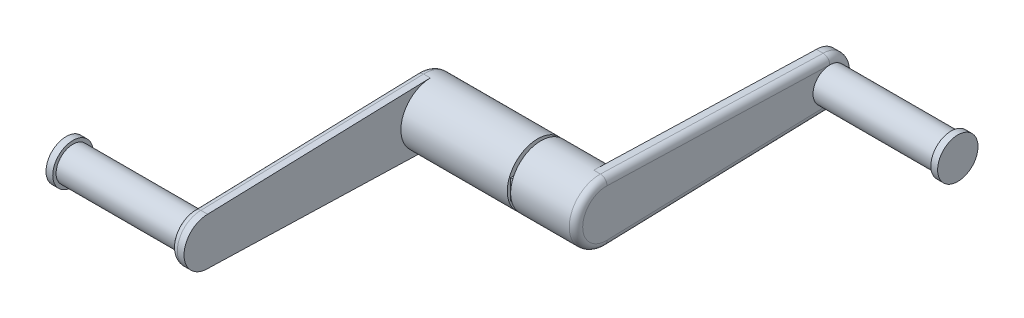
SolidWorks part; units mm, degrees
ref_plane "Front Plane" through (0, 0, 0) normal (0, 0, 1) x (1, 0, 0)
ref_plane "Top Plane" through (0, 0, 0) normal (0, 1, 0) x (1, 0, 0)
ref_plane "Right Plane" through (0, 0, 0) normal (1, 0, 0) x (0, 0, -1)
sketch "Sketch1" plane through (0, 0, 0) normal (1, 0, 0) x (0, 0, -1)
  circle A0 centre (0, 0) radius 338.5
  dimension "D1" = 677
sketch "Sketch2" plane through (0, 0, 0) normal (1, 0, 0) x (0, 0, -1)
  line L0 (-935.3702, 226.3146) -> (-163.5974, 226.3146) construction
  line L1 (-626.7849, -26.0893) -> (-626.7849, -67.6929) construction
  line L2 (-646.7849, -35.9173) -> (-633.3993, -35.9173)
  line L3 (-646.7849, -35.9173) -> (-646.7849, -50.9173)
  line L4 (-646.7849, -50.9173) -> (-633.3993, -50.9173)
  line L5 (-606.7849, -35.9173) -> (-606.7849, -50.9173)
  line L6 (-610.8111, -43.4173) -> (-642.1815, -43.4173) construction
  line L7 (-620.1705, -35.9173) -> (-606.7849, -35.9173)
  line L8 (-620.1705, -50.9173) -> (-606.7849, -50.9173)
  arc A0 (-633.3993, -50.9173) -> (-620.1705, -50.9173) centre (-626.7849, -43.4173) ccw
  arc A1 (-620.1705, -35.9173) -> (-633.3993, -35.9173) centre (-626.7849, -43.4173) ccw
  dimension "D1" = 20
  dimension "D2" = 15
  dimension "D3" = 40
  dimension "D4" = 7.5
  dimension "D5" = 20
sketch "Sketch3" plane through (0, 0, 0) normal (1, 0, 0) x (0, 0, -1)
  circle A0 centre (-626.7849, -43.4173) radius 22.5
  dimension "D1" = 45
extrude "Boss-Extrude1" add sketch "Sketch3" along normal blind 60 and the other way blind 60
sketch "Sketch4" plane through (60, 0, 0) normal (1, 0, 0) x (0, 0, -1)
  line L0 (-460.7849, -25.9173) -> (-626.1061, -20.9275)
  line L1 (-460.7849, -60.9173) -> (-626.1061, -65.907)
  arc A0 (-626.1061, -20.9275) -> (-626.1061, -65.907) centre (-626.7849, -43.4173) ccw
  arc A1 (-460.7849, -60.9173) -> (-460.7849, -25.9173) centre (-460.7849, -43.4173) ccw
  dimension "D1" = 45
  dimension "D2" = 35
  dimension "D3" = 166
extrude "Boss-Extrude2" add sketch "Sketch4" along normal blind 10
sketch "Sketch5" plane through (70, 0, 0) normal (1, 0, 0) x (0, 0, -1)
  circle A0 centre (-460.7849, -43.4173) radius 12.5
  dimension "D1" = 25
extrude "Boss-Extrude3" add sketch "Sketch5" along normal blind 90
sketch "Sketch6" plane through (160, 0, 0) normal (1, 0, 0) x (0, 0, -1)
  circle A0 centre (-460.7849, -43.4173) radius 15
  dimension "D1" = 30
extrude "Boss-Extrude4" add sketch "Sketch6" along normal blind 5
fillet "Fillet1" radius 5 4 edges at (70, -63.4121, 543.4455) (70, -43.4173, 649.2849) (70, -23.4224, 543.4455) (70, -43.4173, 443.2849)
sketch "Sketch7" plane through (-60, 0, 0) normal (-1, 0, 0) x (0, 0, 1)
  line L1 (792.7849, -25.9173) -> (627.4637, -20.9275)
  line L2 (792.7849, -60.9173) -> (627.4637, -65.907)
  arc A0 (627.4637, -20.9275) -> (627.4637, -65.907) centre (626.7849, -43.4173) ccw
  arc A1 (792.7849, -60.9173) -> (792.7849, -25.9173) centre (792.7849, -43.4173) ccw
  dimension "D1" = 45
  dimension "D3" = 35
  dimension "D2" = 166
extrude "Boss-Extrude5" add sketch "Sketch7" along normal blind 10
sketch "Sketch8" plane through (-70, 0, 0) normal (-1, 0, 0) x (0, 0, 1)
  circle A0 centre (792.7849, -43.4173) radius 12.5
  dimension "D1" = 25
extrude "Boss-Extrude6" add sketch "Sketch8" along normal blind 90
sketch "Sketch10" plane through (-160, 0, 0) normal (-1, 0, 0) x (0, 0, 1)
  circle A0 centre (792.7849, -43.4173) radius 15
  dimension "D1" = 30
extrude "Boss-Extrude7" add sketch "Sketch10" along normal blind 5
fillet "Fillet2" radius 5 4 edges at (-70, -63.4122, 710.1243) (-70, -43.4173, 604.2849) (-70, -43.4173, 810.2849) (-70, -23.4224, 710.1243)
ref_plane "Plane2" through (19, 0, 0) normal (1, 0, 0) x (0, 0, -1)
sketch "Sketch12" plane through (19, 0, 0) normal (1, 0, 0) x (0, 0, -1)
  line L0 (-620.1705, -35.9173) -> (-606.7849, -35.9173)
  line L1 (-646.7849, -35.9173) -> (-633.3993, -35.9173)
  line L2 (-646.7849, -35.9173) -> (-646.7849, -50.9173)
  line L3 (-646.7849, -50.9173) -> (-633.3993, -50.9173)
  line L4 (-606.7849, -35.9173) -> (-606.7849, -50.9173)
  line L5 (-620.1705, -50.9173) -> (-606.7849, -50.9173)
  arc A0 (-633.3993, -50.9173) -> (-620.1705, -50.9173) centre (-626.7849, -43.4173) ccw
  arc A1 (-620.1705, -35.9173) -> (-633.3993, -35.9173) centre (-626.7849, -43.4173) ccw
  circle A2 centre (-626.7849, -43.4173) radius 25
  dimension "D1" = 20
  dimension "D6" = 50
  dimension "D2" = 15
  dimension "D3" = 7.5
  dimension "D4" = 40
  dimension "D5" = 20
extrude "Cut-Extrude1" cut sketch "Sketch12" along normal blind 2.5
